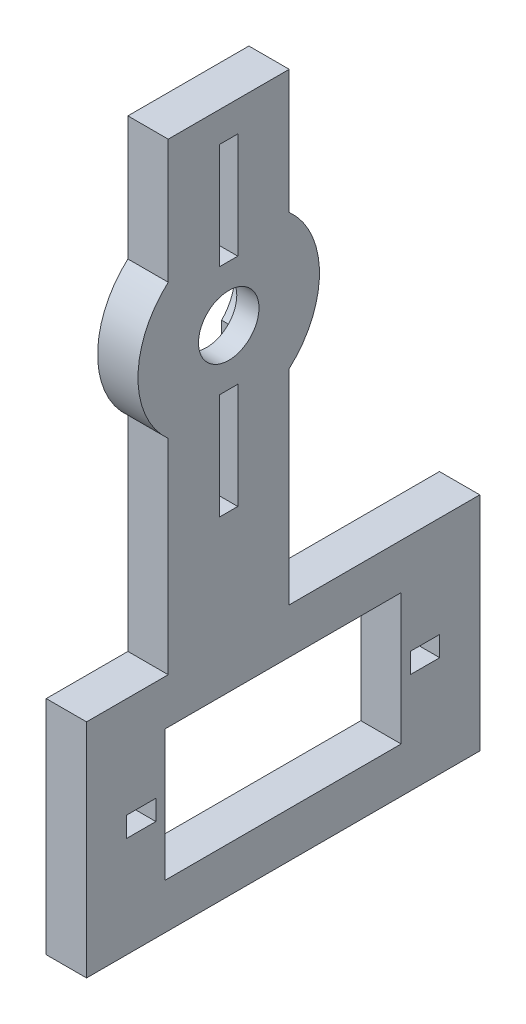
SolidWorks part; units mm, degrees
ref_plane "Front Plane" through (0, 0, 0) normal (0, 0, 1) x (1, 0, 0)
ref_plane "Top Plane" through (0, 0, 0) normal (0, 1, 0) x (1, 0, 0)
ref_plane "Right Plane" through (0, 0, 0) normal (1, 0, 0) x (0, 0, -1)
sketch "Sketch1" plane through (0, 0, 0) normal (1, 0, 0) x (0, 0, -1)
  circle A0 centre (-66, 18) radius 9
extrude "Boss-Extrude1" add sketch "Sketch1" along normal blind 4 from offset 55.6
sketch "Sketch2" plane through (0, 0, 0) normal (0, 0, 1) x (1, 0, 0)
  line L1 (55.6, -12) -> (59.6, -12)
  line L2 (55.6, -12) -> (55.6, 37)
  line L3 (55.6, 37) -> (59.6, 37)
  line L4 (59.6, -12) -> (59.6, 37)
extrude "Boss-Extrude2" add sketch "Sketch2" along normal blind 12 from offset 60
sketch "Sketch3" plane through (0, 0, 0) normal (0, 0, 1) x (1, 0, 0)
  line L1 (55.6, -31) -> (59.6, -31)
  line L2 (55.6, -31) -> (55.6, -9)
  line L3 (55.6, -9) -> (59.6, -9)
  line L4 (59.6, -31) -> (59.6, -9)
extrude "Boss-Extrude3" add sketch "Sketch3" along normal blind 39 from offset 41.1
sketch "Sketch4" plane through (0, 0, 0) normal (1, 0, 0) x (0, 0, -1)
  circle A0 centre (-66, 18) radius 4.6
extrude "Boss-Extrude4" add sketch "Sketch4" along normal blind 2.3 from offset 55.1 separate body
combine bodies "Combine1" operation type subtract main body 103 bodies to subtract 104
sketch "Sketch5" plane through (0, 0, 0) normal (0, 0, 1) x (1, 0, 0)
  line L1 (55.1, 18) -> (57.4, 18)
  line L2 (55.1, 18) -> (55.1, 35.5)
  line L3 (55.1, 35.5) -> (57.4, 35.5)
  line L4 (57.4, 18) -> (57.4, 35.5)
extrude "Boss-Extrude5" add sketch "Sketch5" along normal blind 6.6 from offset 62.7 separate body
combine bodies "Combine2" operation type subtract main body 105 bodies to subtract 106
sketch "Sketch6" plane through (0, 0, 0) normal (0, 0, 1) x (1, 0, 0)
  line L1 (54.6, 23.5) -> (60.6, 23.5)
  line L2 (54.6, 23.5) -> (54.6, 34)
  line L3 (54.6, 34) -> (60.6, 34)
  line L4 (60.6, 23.5) -> (60.6, 34)
extrude "Boss-Extrude6" add sketch "Sketch6" along normal blind 1.8 from offset 65.1 separate body
combine bodies "Combine3" operation type subtract main body 107 bodies to subtract 108
sketch "Sketch7" plane through (0, 0, 0) normal (0, 0, 1) x (1, 0, 0)
  line L1 (55.1, 0.5) -> (57.4, 0.5)
  line L2 (55.1, 0.5) -> (55.1, 18)
  line L3 (55.1, 18) -> (57.4, 18)
  line L4 (57.4, 0.5) -> (57.4, 18)
extrude "Boss-Extrude7" add sketch "Sketch7" along normal blind 6.6 from offset 62.7 separate body
combine bodies "Combine4" operation type subtract main body 109 bodies to subtract 110
sketch "Sketch8" plane through (0, 0, 0) normal (0, 0, 1) x (1, 0, 0)
  line L1 (54.6, 2) -> (60.6, 2)
  line L2 (54.6, 2) -> (54.6, 12.5)
  line L3 (54.6, 12.5) -> (60.6, 12.5)
  line L4 (60.6, 2) -> (60.6, 12.5)
extrude "Boss-Extrude8" add sketch "Sketch8" along normal blind 1.8 from offset 65.1 separate body
combine bodies "Combine5" operation type subtract main body 111 bodies to subtract 112
sketch "Sketch9" plane through (0, 0, 0) normal (1, 0, 0) x (0, 0, -1)
  circle A0 centre (-66, 18) radius 3
extrude "Boss-Extrude9" add sketch "Sketch9" along normal blind 6 from offset 54.6 separate body
combine bodies "Combine6" operation type subtract main body 113 bodies to subtract 114
sketch "Sketch10" plane through (0, 0, 0) normal (0, 0, 1) x (1, 0, 0)
  line L1 (54.6, -26.5) -> (60.6, -26.5)
  line L2 (54.6, -26.5) -> (54.6, -13.5)
  line L3 (54.6, -13.5) -> (60.6, -13.5)
  line L4 (60.6, -26.5) -> (60.6, -13.5)
extrude "Boss-Extrude10" add sketch "Sketch10" along normal blind 23.4 from offset 48.9 separate body
combine bodies "Combine7" operation type subtract main body 115 bodies to subtract 116
sketch "Sketch11" plane through (0, 0, 0) normal (0, 0, 1) x (1, 0, 0)
  line L1 (54.6, -21) -> (60.6, -21)
  line L2 (54.6, -21) -> (54.6, -19)
  line L3 (54.6, -19) -> (60.6, -19)
  line L4 (60.6, -21) -> (60.6, -19)
extrude "Boss-Extrude11" add sketch "Sketch11" along normal blind 2.9 from offset 45.075 separate body
combine bodies "Combine8" operation type subtract main body 117 bodies to subtract 118
sketch "Sketch12" plane through (0, 0, 0) normal (0, 0, 1) x (1, 0, 0)
  line L1 (54.6, -21) -> (60.6, -21)
  line L2 (54.6, -21) -> (54.6, -19)
  line L3 (54.6, -19) -> (60.6, -19)
  line L4 (60.6, -21) -> (60.6, -19)
extrude "Boss-Extrude12" add sketch "Sketch12" along normal blind 2.9 from offset 73.225 separate body
combine bodies "Combine9" operation type subtract main body 119 bodies to subtract 120
